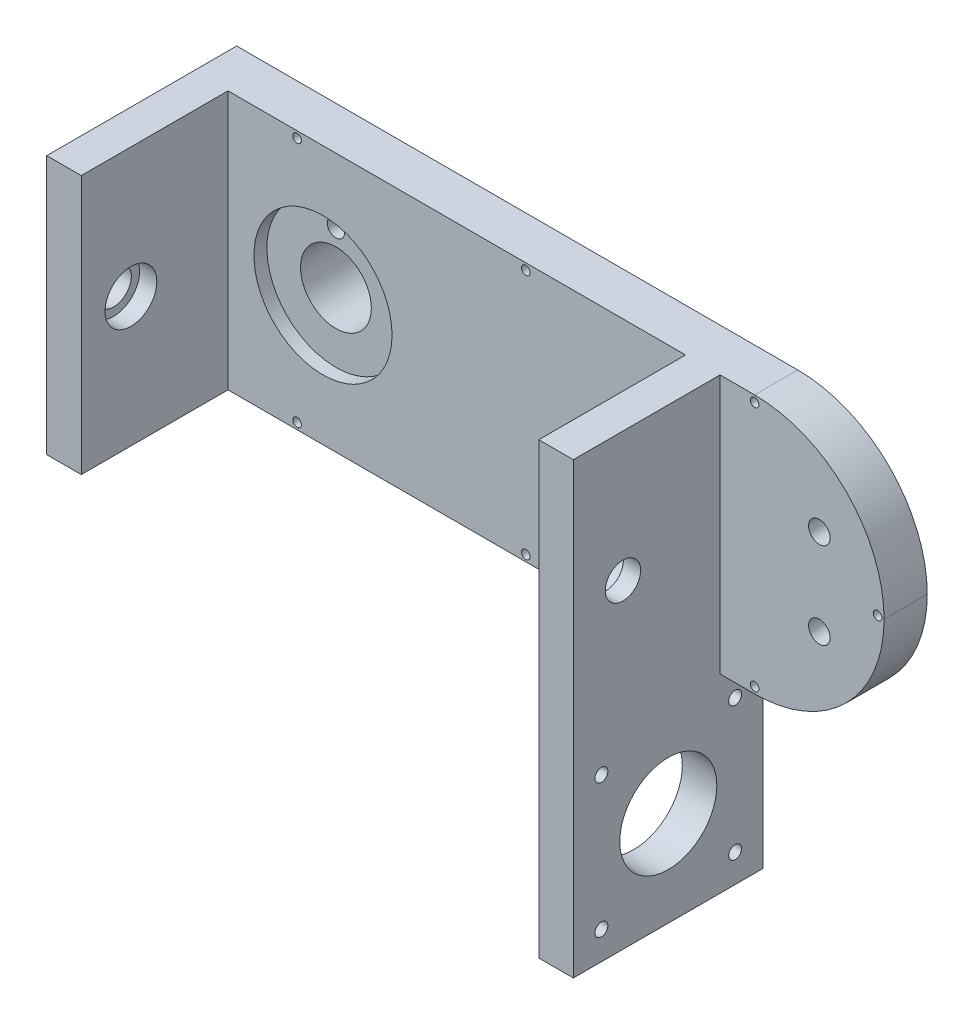
SolidWorks part; units mm, degrees
ref_plane "Front Plane" through (0, 0, 0) normal (0, 0, 1) x (1, 0, 0)
ref_plane "Top Plane" through (0, 0, 0) normal (0, 1, 0) x (1, 0, 0)
ref_plane "Right Plane" through (0, 0, 0) normal (1, 0, 0) x (0, 0, -1)
sketch "Sketch1" plane through (0, 0, 0) normal (0, 0, 1) x (1, 0, 0)
  line L1 (80, -30) -> (-80, -30)
  line L2 (80, -30) -> (80, 30)
  line L3 (80, 30) -> (-80, 30)
  line L4 (-80, -30) -> (-80, 30)
  line L5 (80, -30) -> (-80, 30) construction
  line L6 (80, 30) -> (-80, -30) construction
  point P0 (0, 0)
  dimension "D1" = 60
  dimension "D2" = 160
extrude "Boss-Extrude1" add sketch "Sketch1" along normal mid plane 10
sketch "Sketch4" plane through (0, 0, 5) normal (0, 0, 1) x (1, 0, 0)
  line L0 (34, 30) -> (34, -30)
  line L1 (34, 30) -> (42, 30)
  line L2 (34, -30) -> (42, -30)
  line L3 (42, 30) -> (42, -30)
  line L6 (80, -30) -> (80, 30) construction
  line L7 (0, 0) -> (42, 0) construction
  dimension "D1" = 8
  dimension "D2" = 38
  dimension "D3" = 60
extrude "Boss-Extrude3" add sketch "Sketch4" along normal blind 34
sketch "Sketch5" plane through (42, 0, 0) normal (1, 0, 0) x (0, 0, -1)
  line L0 (-27.5, 0) -> (0, 0) construction
  line L2 (-27.5, -18.25) -> (-27.5, 18.25) construction
  line L4 (-5, -30) -> (-5, 30)
  line L5 (-5, 30) -> (-39, 30)
  line L6 (-39, 30) -> (-39, -30)
  line L7 (-39, -30) -> (-5, -30)
  line L8 (-5, -30) -> (-5, 30) construction
  line L9 (-5, 30) -> (-39, 30) construction
  line L10 (-39, 30) -> (-39, -30) construction
  line L11 (-39, -30) -> (-5, -30) construction
  circle A2 centre (-27.5, 0) radius 4.1
  point P7 (-27.5, 0)
  dimension "D5" = 8.2
  dimension "D2" = 36.5
  dimension "D6" = 22.5
  dimension "D1" = 0
extrude "Cut-Extrude2" cut sketch "Sketch5" against normal up to next
sketch "Sketch6" plane through (0, 0, -5) normal (0, 0, -1) x (-1, 0, 0)
  line L0 (0, -30) -> (0, 30) construction
  line L1 (-80, 30) -> (80, 30) construction
  line L2 (80, 30) -> (80, -30) construction
  circle A0 centre (50, 0) radius 10
  point P8 (0, 0)
  dimension "D1" = 20
  dimension "D2" = 30
extrude "Boss-Extrude4" add sketch "Sketch6" along normal blind 12
sketch "Sketch7" plane through (0, 0, -17) normal (0, 0, -1) x (-1, 0, 0)
  circle A0 centre (50, 0) radius 4.2
  dimension "D1" = 8.4
extrude "Cut-Extrude3" cut sketch "Sketch7" against normal up to next
pattern_linear "LPattern1" count 2 spacing 114 along (-1, 0, 0) of "Boss-Extrude3"
sketch "Sketch8" plane through (-72, 0, -55) normal (1, 0, 0) x (0, 0, -1)
  line L3 (-82.5, 0) -> (2.8547, 0) construction
  circle A2 centre (-82.5, 0) radius 4.1
  point P7 (-82.5, 0)
  dimension "D5" = 8.2
  dimension "D1" = 85.3547
extrude "Cut-Extrude4" cut sketch "Sketch8" against normal up to next
sketch "Sketch9" plane through (0, 0, 5) normal (0, 0, 1) x (1, 0, 0)
  line L0 (65, 30) -> (65, -30) construction
  line L1 (80, 30) -> (42, 30) construction
  line L2 (42, -30) -> (80, -30) construction
  line L3 (42, -30) -> (42, 30) construction
  line L4 (42, 0) -> (80, 0) construction
  line L5 (80, -30) -> (80, 30) construction
  circle A0 centre (65, 10) radius 2.5
  circle A1 centre (65, -10) radius 2.5
  dimension "D2" = 5
  dimension "D1" = 23
  dimension "D3" = 20
extrude "Cut-Extrude5" cut sketch "Sketch9" against normal up to next
fillet "Fillet1" radius 30 2 edges at (80, 30, 0) (80, -30, 0)
sketch "Sketch12" plane through (0, 0, 5) normal (0, 0, 1) x (1, 0, 0)
  line L0 (50, 30) -> (50, -30) construction
  line L1 (0, 0) -> (80, 0) construction
  line L2 (50, 28.5) -> (-29.2019, 28.5) construction
  line L3 (50, -28.5) -> (-29.2019, -28.5) construction
  circle A0 centre (-3, 28.5) radius 1
  circle A1 centre (-56, 28.5) radius 1
  arc A2 (50, -28.5) -> (50, 28.5) centre (50, 0) ccw construction
  circle A3 centre (78.5, 0) radius 1
  circle A4 centre (50, 28.5) radius 1
  circle A5 centre (-3, -28.5) radius 1
  circle A6 centre (-56, -28.5) radius 1
  circle A7 centre (50, -28.5) radius 1
  dimension "D1" = 57
  dimension "D2" = 2
  dimension "D3" = 2
  dimension "D4" = 3
  dimension "D5" = 2
extrude "Cut-Extrude7" cut sketch "Sketch12" against normal up to next
sketch "Sketch15" plane through (0, 0, 5) normal (0, 0, 1) x (1, 0, 0)
  circle A0 centre (-50, 0) radius 16
  dimension "D1" = 32
extrude "Cut-Extrude11" cut sketch "Sketch15" against normal blind 3
sketch "Sketch16" plane through (0, 0, 2) normal (0, 0, 1) x (1, 0, 0)
  circle A0 centre (-50, 0) radius 8.2
  dimension "D1" = 16.4
extrude "Cut-Extrude12" cut sketch "Sketch16" against normal blind 12
sketch "Sketch17" plane through (0, 0, 2) normal (0, 0, 1) x (1, 0, 0)
  circle A0 centre (-50, 0) radius 12 construction
  circle A1 centre (-50, 12) radius 2
  circle A2 centre (-38, 15) radius 2
  circle A3 centre (-35, 3) radius 2
  circle A4 centre (-47, 0) radius 2
  point P14 (-42.5, 7.5)
  dimension "D1" = 24
  dimension "D2" = 4
  dimension "D3" = 4
extrude "Cut-Extrude13" cut sketch "Sketch17" against normal blind 3
sketch "Sketch18" plane through (0, -30, 0) normal (0, 1, 0) x (1, 0, 0)
  line L0 (34, -5) -> (34, 5) construction
  line L1 (50, 5) -> (-80, 5) construction
  line L3 (34, 5) -> (42, 5)
  line L4 (34, 5) -> (34, -39)
  line L5 (34, -39) -> (42, -39)
  line L6 (42, 5) -> (42, -39)
  line L7 (38, -39) -> (38, 5) construction
  line L8 (34, -17) -> (42, -17) construction
  point P688 (38, -17)
  dimension "D1" = 44
extrude "Boss-Extrude5" add sketch "Sketch18" against normal blind 44
sketch "Sketch20" plane through (42, 0, 0) normal (1, 0, 0) x (0, 0, -1)
  line L1 (-39, -74) -> (5, -74) construction
  line L2 (-39, -74) -> (-39, -30) construction
  line L3 (-39, -30) -> (5, -30) construction
  line L4 (5, -74) -> (5, -30) construction
  line L5 (-17, -30) -> (-17, -74) construction
  line L6 (-39, -52) -> (5, -52) construction
  circle A0 centre (-32.5, -36.5) radius 1.5
  circle A1 centre (-1.5, -36.5) radius 1.5
  circle A2 centre (-1.5, -67.5) radius 1.5
  circle A3 centre (-32.5, -67.5) radius 1.5
  circle A4 centre (-17, -52) radius 11.25
  point P17 (-17, -52)
  point P152 (-17, -52)
  dimension "D1" = 3
  dimension "D4" = 22.5
  dimension "D2" = 31
  dimension "D3" = 31
extrude "Cut-Extrude15" cut sketch "Sketch20" against normal up to next
sketch "Sketch21" plane through (-72, 0, 0) normal (1, 0, 0) x (0, 0, -1)
  circle A0 centre (-27.5, 0) radius 4.1 construction
  circle A1 centre (-27.5, 0) radius 4.1 construction
  circle A2 centre (-27.5, 0) radius 6
  dimension "D1" = 12
extrude "Cut-Extrude16" cut sketch "Sketch21" against normal blind 4
sketch "Sketch22" plane through (34, 0, 0) normal (-1, 0, 0) x (0, 0, 1)
  circle A0 centre (27.5, 0) radius 6
  dimension "D1" = 12
extrude "Cut-Extrude17" cut sketch "Sketch22" against normal blind 4
